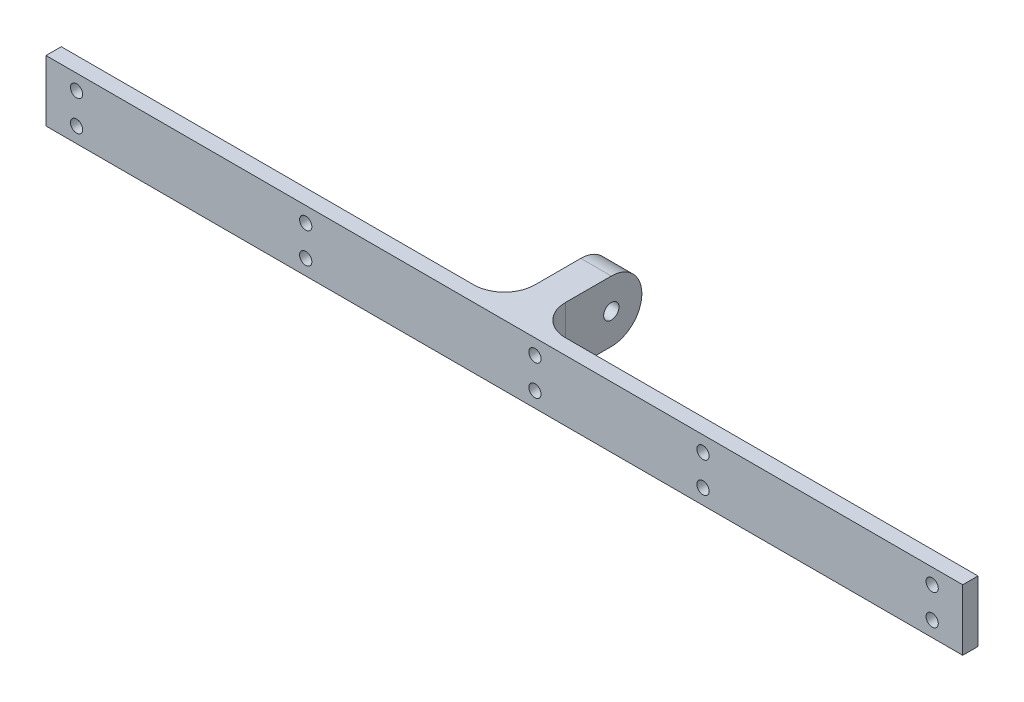
SolidWorks part; units mm, degrees
ref_plane "Plan de face" through (0, 0, 0) normal (0, 0, 1) x (1, 0, 0)
ref_plane "Plan de dessus" through (0, 0, 0) normal (0, 1, 0) x (1, 0, 0)
ref_plane "Plan de droite" through (0, 0, 0) normal (1, 0, 0) x (0, 0, -1)
sketch "Esquisse1" plane through (0, 0, 0) normal (0, 0, 1) x (1, 0, 0)
  line L1 (-150, 10) -> (150, 10)
  line L2 (-150, 10) -> (-150, -10)
  line L3 (-150, -10) -> (150, -10)
  line L4 (150, 10) -> (150, -10)
  dimension "D1" = 150
  dimension "D2" = 300
  dimension "D3" = 20
  dimension "D4" = 10
extrude "Boss.-Extru.1" add sketch "Esquisse1" along normal blind 5
sketch "Esquisse2" plane through (0, 0, 5) normal (0, 0, 1) x (1, 0, 0)
  line L0 (-150, 10) -> (-150, -10) construction
  line L1 (-150, -10) -> (150, -10) construction
  line L2 (150, 10) -> (-150, 10) construction
  line L3 (150, 10) -> (-150, 10) construction
  line L4 (150, -10) -> (150, 10) construction
  circle A0 centre (-140, 5) radius 2
  circle A1 centre (-140, -5) radius 2
  circle A2 centre (-65, 5) radius 2
  circle A3 centre (-65, -5) radius 2
  circle A4 centre (10, 5) radius 2
  circle A5 centre (10, -5) radius 2
  circle A6 centre (65, 5) radius 2
  circle A7 centre (65, -5) radius 2
  circle A8 centre (140, 5) radius 2
  circle A9 centre (140, -5) radius 2
  dimension "D1" = 4
  dimension "D2" = 4
  dimension "D3" = 4
  dimension "D4" = 4
  dimension "D5" = 4
  dimension "D6" = 4
  dimension "D7" = 4
  dimension "D8" = 4
  dimension "D9" = 4
  dimension "D10" = 4
  dimension "D16" = 5
  dimension "D17" = 5
  dimension "D18" = 5
  dimension "D19" = 5
  dimension "D20" = 5
  dimension "D21" = 5
  dimension "D22" = 5
  dimension "D23" = 10
  dimension "D24" = 10
  dimension "D25" = 85
  dimension "D26" = 85
  dimension "D27" = 140
  dimension "D28" = 140
  dimension "D29" = 85
  dimension "D30" = 85
  dimension "D11" = 10
  dimension "D12" = 10
  dimension "D13" = 5
  dimension "D14" = 5
  dimension "D15" = 5
extrude "Enlèv. mat.-Extru.1" cut sketch "Esquisse2" against normal blind 5
sketch "Esquisse3" plane through (0, 0, 0) normal (0, 0, -1) x (-1, 0, 0)
  line L0 (150, -10) -> (-150, -10) construction
  line L1 (-5, -10) -> (5, -10)
  line L2 (-5, -10) -> (-5, 10)
  line L3 (-5, 10) -> (5, 10)
  line L4 (5, -10) -> (5, 10)
  line L5 (-150, 10) -> (150, 10) construction
  dimension "D1" = 5
  dimension "D2" = 5
extrude "Boss.-Extru.2" add sketch "Esquisse3" along normal blind 35
fillet "Congé1" radius 10 2 edges at (-5, 0, 0) (5, 0, 0)
fillet "Congé2" radius 10 2 edges at (0, -10, -35) (0, 10, -35)
sketch "Esquisse4" plane through (-5, 0, 0) normal (-1, 0, 0) x (0, 0, 1)
  line L0 (-25, 10) -> (-10, 10) construction
  circle A0 centre (-25, 0) radius 1.5
  dimension "D1" = 3
  dimension "D2" = 10
  dimension "D3" = 10
extrude "Enlèv. mat.-Extru.2" cut sketch "Esquisse4" against normal blind 35
sketch "Esquisse6" plane through (5, 0, 0) normal (1, 0, 0) x (0, 0, -1)
  circle A0 centre (25, 0) radius 2.5
  dimension "D1" = 5
extrude "Enlèv. mat.-Extru.3" cut sketch "Esquisse6" against normal blind 5
